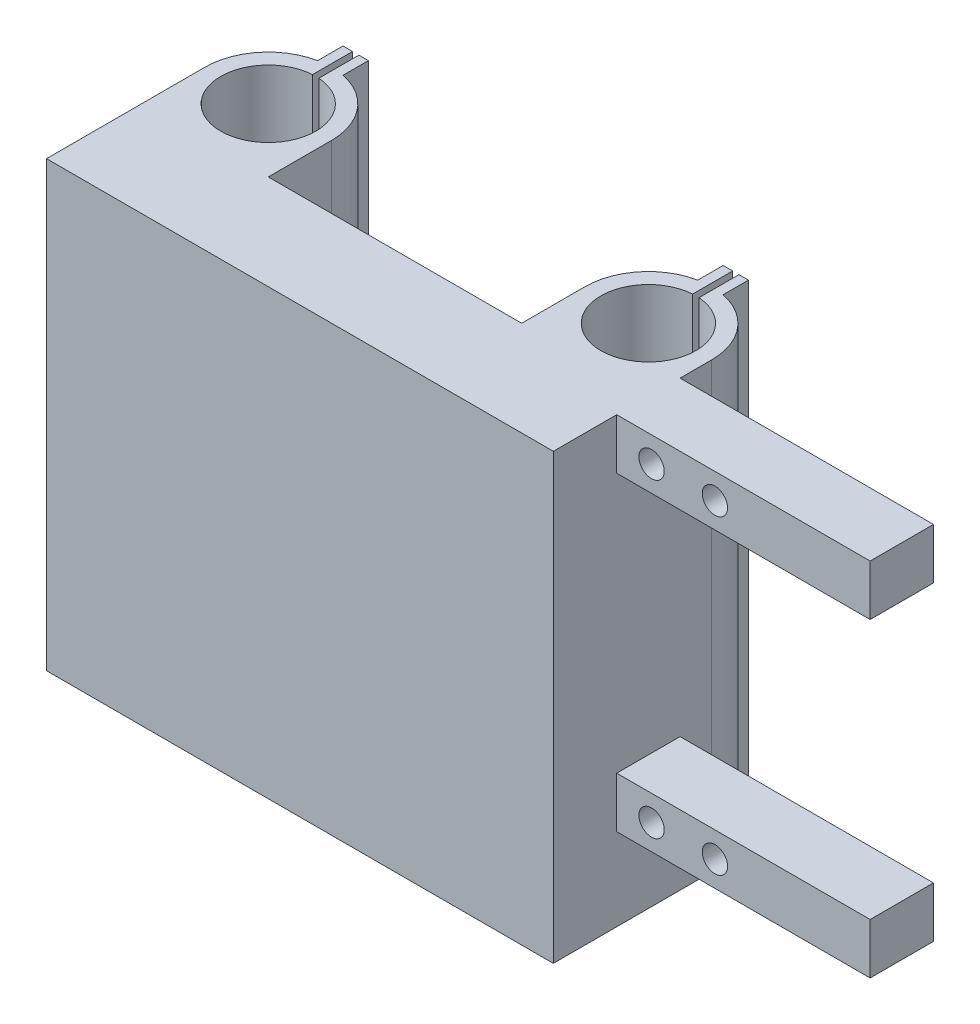
SolidWorks part; units mm, degrees
ref_plane "Alzado" through (0, 0, 0) normal (0, 0, 1) x (1, 0, 0)
ref_plane "Planta" through (0, 0, 0) normal (0, 1, 0) x (1, 0, 0)
ref_plane "Vista lateral" through (0, 0, 0) normal (1, 0, 0) x (0, 0, -1)
sketch "Croquis1" plane through (0, 0, 0) normal (0, 1, 0) x (1, 0, 0)
  line L0 (-58.0166, 0) -> (58.0166, 0) construction
  line L5 (40, -25) -> (40, 0)
  line L6 (11.3137, 4) -> (20.8348, 4)
  line L7 (0, 33.1459) -> (0, -45.5761) construction
  line L8 (-40, -25) -> (-40, 0)
  line L9 (-11.3137, 4) -> (-20.8348, 4)
  line L10 (-40, -25) -> (40, -25)
  arc A1 (11.3137, 4) -> (-11.3137, 4) centre (0, 0) ccw
  arc A2 (40, 0) -> (20.8348, 4) centre (30, 0) ccw
  arc A3 (-40, 0) -> (-20.8348, 4) centre (-30, 0) cw
  point P3 (0, 0)
  dimension "D1" = 20
  dimension "D2" = 24
  dimension "D3" = 30
  dimension "D4" = 4
  dimension "D5" = 25
extrude "Saliente-Extruir1" add sketch "Croquis1" along normal blind 70
sketch "Croquis3" plane through (0, 70, 0) normal (0, 1, 0) x (1, 0, 0)
  line L0 (-30, 0) -> (-30, 16.5211) construction
  line L1 (-32, 9.798) -> (-32, 13.798)
  line L2 (-32, 13.798) -> (-28, 13.798)
  line L3 (-28, 9.798) -> (-28, 13.798)
  line L4 (0, -55) -> (0, 55) construction
  line L5 (28, 9.798) -> (28, 13.798)
  line L6 (32, 13.798) -> (28, 13.798)
  line L7 (32, 9.798) -> (32, 13.798)
  arc A0 (-20.8348, 4) -> (-40, 0) centre (-30, 0) ccw construction
  arc A1 (-28, 9.798) -> (-32, 9.798) centre (-30, 0) ccw
  arc A2 (28, 9.798) -> (32, 9.798) centre (30, 0) cw
  point P10 (-30, 13.798)
  dimension "D1" = 4
  dimension "D2" = 4
extrude "Saliente-Extruir2" add sketch "Croquis3" against normal up to surface (70 mm away) up to face at (0, 0, 1.3027)
sketch "Croquis4" plane through (0, 70, 0) normal (0, 1, 0) x (1, 0, 0)
  line L0 (-30.5, 7.4833) -> (-30.5, 14.6548)
  line L1 (-30, 0) -> (-30, 16.6168) construction
  line L2 (-30.5, 14.6548) -> (-29.5, 14.6548)
  line L3 (-29.5, 7.4833) -> (-29.5, 14.6548)
  line L4 (0, -55) -> (0, 55) construction
  line L5 (29.5, 7.4833) -> (29.5, 14.6548)
  line L6 (30.5, 14.6548) -> (29.5, 14.6548)
  line L7 (30.5, 7.4833) -> (30.5, 14.6548)
  arc A1 (-30.5, 7.4833) -> (-29.5, 7.4833) centre (-30, 0) ccw
  arc A2 (30.5, 7.4833) -> (29.5, 7.4833) centre (30, 0) cw
  point P8 (-30, 14.6548)
  point P16 (30, 14.6548)
  dimension "D1" = 15
  dimension "D2" = 1
extrude "Cortar-Extruir2" cut sketch "Croquis4" against normal through all both and the other way through all
sketch "Croquis5" plane through (0, 70, 0) normal (0, 1, 0) x (1, 0, 0)
  line L0 (-20, 0) -> (-20, -10)
  line L1 (-20, -10) -> (20, -10)
  line L2 (0, 31.6012) -> (0, -31.6012) construction
  line L3 (-20, -10) -> (-30, -10) construction
  line L7 (20, 0) -> (20, -10)
  line L8 (-20.8348, 4) -> (-20.8348, 13.996)
  line L9 (-20.8348, 13.996) -> (20.8348, 13.996)
  line L10 (20.8348, 13.996) -> (20.8348, 4)
  arc A0 (11.3137, 4) -> (-11.3137, 4) centre (0, 0) ccw construction
  arc A3 (-32, 9.798) -> (-40, 0) centre (-30, 0) ccw construction
  arc A4 (-32, 9.798) -> (-40, 0) centre (-30, 0) ccw construction
  arc A5 (-20, 0) -> (-20.8348, 4) centre (-30, 0) ccw
  arc A6 (-32, 9.798) -> (-40, 0) centre (-30, 0) ccw construction
  arc A7 (20, 0) -> (20.8348, 4) centre (30, 0) cw
  point P9 (0, 0)
  point P16 (0, -10)
extrude "Cortar-Extruir3" cut sketch "Croquis5" against normal blind 30
sketch "Croquis9" plane through (0, 0, 0) normal (0, 1, 0) x (1, 0, 0)
  line L0 (-20, 0) -> (-20, -10)
  line L1 (-20, -10) -> (20, -10)
  line L2 (0, 31.6012) -> (0, -31.6012) construction
  line L3 (-20, -10) -> (-30, -10) construction
  line L7 (20, 0) -> (20, -10)
  line L8 (-20.8348, 4) -> (-20.8348, 13.996)
  line L9 (-20.8348, 13.996) -> (20.8348, 13.996)
  line L10 (20.8348, 13.996) -> (20.8348, 4)
  arc A4 (-32, 9.798) -> (-40, 0) centre (-30, 0) ccw construction
  arc A5 (-20, 0) -> (-20.8348, 4) centre (-30, 0) ccw
  arc A6 (-32, 9.798) -> (-40, 0) centre (-30, 0) ccw construction
  arc A7 (20, 0) -> (20.8348, 4) centre (30, 0) cw
  point P9 (0, 0)
  point P16 (0, -10)
extrude "Cortar-Extruir6" cut sketch "Croquis9" along normal blind 30 contours L9 L10 A7 L7 L1 L0 A5 L8
sketch "Croquis6" plane through (0, 70, 0) normal (0, 1, 0) x (1, 0, 0)
  line L0 (0, 0) -> (-12.9386, 12.9386) construction
  line L1 (0, 0) -> (0, 16.0434) construction
  circle A0 centre (0, 0) radius 5
  circle A1 centre (-6.0104, 6.0104) radius 1.6
  circle A2 centre (6.0104, 6.0104) radius 1.6
  circle A3 centre (6.0104, -6.0104) radius 1.6
  circle A4 centre (-6.0104, -6.0104) radius 1.6
  point P16 (0, 0)
  dimension "D1" = 10
  dimension "D3" = 3.2
  dimension "D4" = 8.5
  dimension "D2" = 45
  dimension "D5" = 4
extrude "Cortar-Extruir4" cut sketch "Croquis6" against normal through all both and the other way through all
sketch "Croquis7" plane through (40, 0, 0) normal (1, 0, 0) x (0, 0, -1)
  line L0 (-15, 70) -> (-15, 62)
  line L1 (-25, 70) -> (0, 70) construction
  line L2 (-15, 62) -> (-5, 62)
  line L3 (-35.4515, 41.5) -> (26.4894, 41.5) construction
  line L4 (-5, 62) -> (-5, 70)
  line L5 (-5, 70) -> (-15, 70)
  line L6 (-25, 70) -> (-25, 0) construction
  line L7 (-5, 13) -> (-15, 13)
  line L8 (-5, 21) -> (-5, 13)
  line L9 (-15, 21) -> (-5, 21)
  line L10 (-15, 13) -> (-15, 21)
  dimension "D1" = 8
  dimension "D2" = 20.5
  dimension "D3" = 10
  dimension "D4" = 10
extrude "Saliente-Extruir3" add sketch "Croquis7" along normal blind 40
sketch "Croquis8" plane through (0, 0, 15) normal (0, 0, 1) x (1, 0, 0)
  line L0 (50.5, 62) -> (50.5, 21) construction
  line L1 (80, 62) -> (40, 62) construction
  line L2 (49.485, 41.5) -> (51.515, 41.5) construction
  line L3 (80, 21) -> (40, 21) construction
  line L7 (40, 70) -> (40, 0) construction
  circle A0 centre (45.5, 66) radius 2
  circle A1 centre (55.5, 66) radius 2
  circle A2 centre (45.5, 17) radius 2
  circle A3 centre (55.5, 17) radius 2
  point P4 (55, 62)
  point P5 (52.008, 62)
  point P6 (50, 65.6825)
  point P9 (50.5, 41.5)
  point P10 (55, 62)
  point P11 (55, 21)
  point P12 (55, 21)
  point P13 (55, 62)
  point P14 (63.5555, 41.5)
  point P21 (0, 0)
  point P22 (0, 0)
  point P24 (55, 21)
  point P26 (51.7384, 21)
  dimension "D1" = 10
  dimension "D2" = 4
  dimension "D3" = 5.5
  dimension "D4" = 49
extrude "Cortar-Extruir5" cut sketch "Croquis8" against normal through all both and the other way through all
